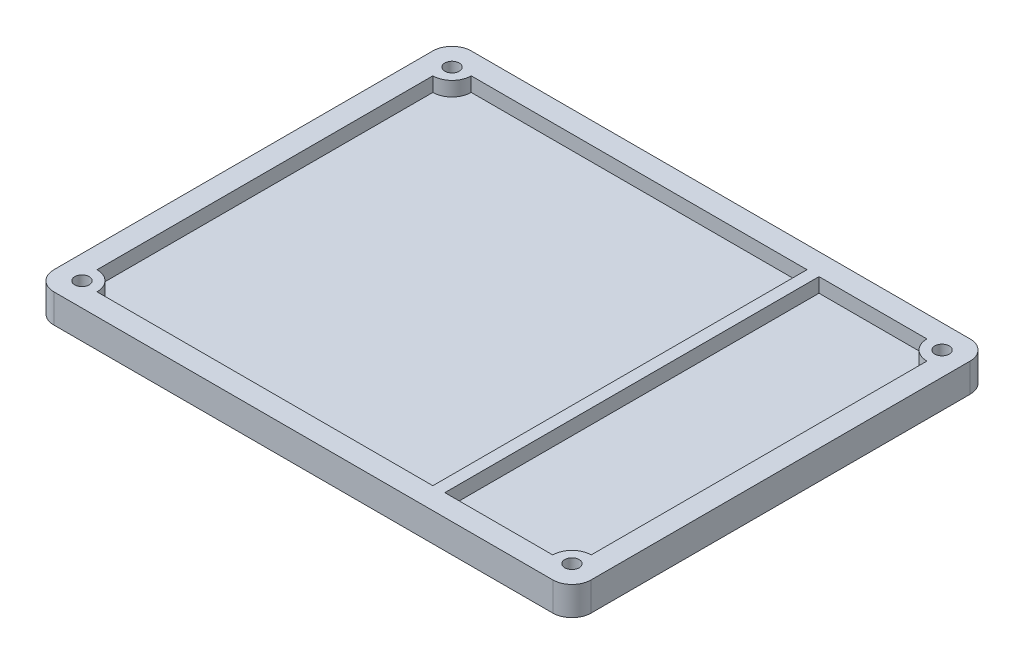
SolidWorks part; units mm, degrees
ref_plane "Front Plane" through (0, 0, 0) normal (0, 0, 1) x (1, 0, 0)
ref_plane "Top Plane" through (0, 0, 0) normal (0, 1, 0) x (1, 0, 0)
ref_plane "Right Plane" through (0, 0, 0) normal (1, 0, 0) x (0, 0, -1)
sketch "Sketch2" plane through (0, 0, 0) normal (0, 1, 0) x (1, 0, 0)
  line L0 (22.2847, 38.8731) -> (24.7847, 38.8731)
  line L1 (22.2847, -39.1269) -> (24.7847, -39.1269)
  line L2 (47.2847, 38.8731) -> (24.7847, 38.8731)
  line L3 (22.2847, 38.8731) -> (-47.7153, 38.8731)
  line L4 (51.2847, -35.1269) -> (51.2847, 34.8731)
  line L5 (24.7847, -39.1269) -> (47.2847, -39.1269)
  line L6 (-47.7153, -39.1269) -> (22.2847, -39.1269)
  line L7 (-51.7153, 34.8731) -> (-51.7153, -35.1269)
  line L8 (53.7847, -39.6269) -> (53.7847, 39.3731)
  line L9 (-52.2153, -41.6269) -> (51.7847, -41.6269)
  line L10 (-54.2153, -39.6269) -> (-54.2153, 39.3731)
  line L11 (51.7847, 41.3731) -> (-52.2153, 41.3731)
  circle A0 centre (50.8596, -38.7018) radius 1.5
  circle A1 centre (-51.2902, -38.7018) radius 1.5
  circle A2 centre (50.8596, 38.448) radius 1.5
  circle A3 centre (-51.2902, 38.448) radius 1.5
  arc A4 (47.2847, 38.8731) -> (51.2847, 34.8731) centre (51.2847, 38.8731) ccw
  arc A5 (51.2847, -35.1269) -> (47.2847, -39.1269) centre (51.2847, -39.1269) ccw
  arc A6 (-47.7153, -39.1269) -> (-51.7153, -35.1269) centre (-51.7153, -39.1269) ccw
  arc A7 (-51.7153, 34.8731) -> (-47.7153, 38.8731) centre (-51.7153, 38.8731) ccw
  arc A8 (53.7847, 39.3731) -> (51.7847, 41.3731) centre (51.7847, 39.3731) ccw
  arc A9 (51.7847, -41.6269) -> (53.7847, -39.6269) centre (51.7847, -39.6269) ccw
  arc A10 (-54.2153, -39.6269) -> (-52.2153, -41.6269) centre (-52.2153, -39.6269) ccw
  arc A11 (-52.2153, 41.3731) -> (-54.2153, 39.3731) centre (-52.2153, 39.3731) ccw
  point P4 (50.8596, 38.448)
extrude "Boss-Extrude1" add sketch "Sketch2" along normal blind 3
sketch "Sketch3" plane through (0, 0, 0) normal (0, -1, 0) x (1, 0, 0)
  line L0 (53.7847, 39.6269) -> (53.7847, -39.3731) construction
  line L1 (51.7847, -41.3731) -> (-52.2153, -41.3731) construction
  line L2 (-54.2153, -39.3731) -> (-54.2153, 39.6269) construction
  line L3 (-52.2153, 41.6269) -> (51.7847, 41.6269) construction
  line L4 (53.7847, 39.6269) -> (53.7847, -39.3731)
  line L5 (51.7847, -41.3731) -> (-52.2153, -41.3731)
  line L6 (-54.2153, -39.3731) -> (-54.2153, 39.6269)
  line L7 (-52.2153, 41.6269) -> (51.7847, 41.6269)
  arc A0 (53.7847, 39.6269) -> (51.7847, 41.6269) centre (51.7847, 39.6269) ccw construction
  arc A1 (51.7847, -41.3731) -> (53.7847, -39.3731) centre (51.7847, -39.3731) ccw construction
  arc A2 (-54.2153, -39.3731) -> (-52.2153, -41.3731) centre (-52.2153, -39.3731) ccw construction
  arc A3 (-52.2153, 41.6269) -> (-54.2153, 39.6269) centre (-52.2153, 39.6269) ccw construction
  arc A4 (53.7847, 39.6269) -> (51.7847, 41.6269) centre (51.7847, 39.6269) ccw
  arc A5 (51.7847, -41.3731) -> (53.7847, -39.3731) centre (51.7847, -39.3731) ccw
  arc A6 (-54.2153, -39.3731) -> (-52.2153, -41.3731) centre (-52.2153, -39.3731) ccw
  arc A7 (-52.2153, 41.6269) -> (-54.2153, 39.6269) centre (-52.2153, 39.6269) ccw
extrude "Boss-Extrude2" add sketch "Sketch3" along normal blind 3
sketch "Sketch4" plane through (0, 3, 0) normal (0, 1, 0) x (1, 0, 0)
  circle A0 centre (50.8596, 38.448) radius 1.5 construction
  circle A1 centre (50.8596, -38.7018) radius 1.5 construction
  circle A2 centre (-51.2902, -38.7018) radius 1.5 construction
  circle A3 centre (-51.2902, 38.448) radius 1.5 construction
  circle A4 centre (50.8596, 38.448) radius 1.5
  circle A5 centre (50.8596, -38.7018) radius 1.5
  circle A6 centre (-51.2902, -38.7018) radius 1.5
  circle A7 centre (-51.2902, 38.448) radius 1.5
extrude "Cut-Extrude1" cut sketch "Sketch4" against normal up to surface (6 mm away) up to face at (-0.2153, -3, 0.1269)
sketch "Sketch6" plane through (0, 3, 0) normal (0, 1, 0) x (1, 0, 0)
  line L6 (-56.2153, 39.3731) -> (-56.2153, -39.6269)
  line L7 (51.7847, 43.3731) -> (-52.2153, 43.3731)
  line L8 (-56.2153, 39.3731) -> (-56.2153, -39.6269)
  line L9 (51.7847, 43.3731) -> (-52.2153, 43.3731)
  line L15 (53.7847, -39.6269) -> (53.7847, 39.3731) construction
  line L16 (-52.2153, -41.6269) -> (51.7847, -41.6269) construction
  line L17 (55.7847, -39.6269) -> (55.7847, 39.3731)
  line L18 (-52.2153, -43.6269) -> (51.7847, -43.6269)
  line L19 (55.7847, -39.6269) -> (55.7847, 39.3731)
  line L20 (-52.2153, -43.6269) -> (51.7847, -43.6269)
  line L21 (-54.2153, 39.3731) -> (-54.2153, -39.6269) construction
  line L22 (51.7847, 41.3731) -> (-52.2153, 41.3731) construction
  line L23 (53.7847, -39.6269) -> (53.7847, 39.3731)
  line L24 (-52.2153, -41.6269) -> (51.7847, -41.6269)
  line L25 (-54.2153, 39.3731) -> (-54.2153, -39.6269)
  line L26 (51.7847, 41.3731) -> (-52.2153, 41.3731)
  arc A3 (-52.2153, 43.3731) -> (-56.2153, 39.3731) centre (-52.2153, 39.3731) ccw
  arc A4 (-52.2153, 43.3731) -> (-56.2153, 39.3731) centre (-52.2153, 39.3731) ccw
  arc A15 (53.7847, 39.3731) -> (51.7847, 41.3731) centre (51.7847, 39.3731) ccw construction
  arc A16 (51.7847, -41.6269) -> (53.7847, -39.6269) centre (51.7847, -39.6269) ccw construction
  arc A17 (-54.2153, -39.6269) -> (-52.2153, -41.6269) centre (-52.2153, -39.6269) ccw construction
  arc A18 (55.7847, 39.3731) -> (51.7847, 43.3731) centre (51.7847, 39.3731) ccw
  arc A19 (51.7847, -43.6269) -> (55.7847, -39.6269) centre (51.7847, -39.6269) ccw
  arc A20 (-56.2153, -39.6269) -> (-52.2153, -43.6269) centre (-52.2153, -39.6269) ccw
  arc A21 (55.7847, 39.3731) -> (51.7847, 43.3731) centre (51.7847, 39.3731) ccw
  arc A22 (51.7847, -43.6269) -> (55.7847, -39.6269) centre (51.7847, -39.6269) ccw
  arc A23 (-56.2153, -39.6269) -> (-52.2153, -43.6269) centre (-52.2153, -39.6269) ccw
  arc A24 (-52.2153, 41.3731) -> (-54.2153, 39.3731) centre (-52.2153, 39.3731) ccw construction
  arc A25 (53.7847, 39.3731) -> (51.7847, 41.3731) centre (51.7847, 39.3731) ccw
  arc A26 (51.7847, -41.6269) -> (53.7847, -39.6269) centre (51.7847, -39.6269) ccw
  arc A27 (-54.2153, -39.6269) -> (-52.2153, -41.6269) centre (-52.2153, -39.6269) ccw
  arc A28 (-52.2153, 41.3731) -> (-54.2153, 39.3731) centre (-52.2153, 39.3731) ccw
  dimension "D1" = 2
  dimension "D2" = 2
extrude "Boss-Extrude3" add sketch "Sketch6" against normal up to surface (6 mm away) up to face at (-51.2902, -3, -39.948)
sketch "Sketch7" plane through (0, -3, 0) normal (0, -1, 0) x (1, 0, 0)
  circle A0 centre (-51.2902, 38.7018) radius 3
  circle A1 centre (50.8596, 38.7018) radius 3
  circle A2 centre (-51.2902, -38.448) radius 3
  circle A3 centre (50.8596, -38.448) radius 3
  dimension "D1" = 6
  dimension "D2" = 6
  dimension "D3" = 6
  dimension "D4" = 6
extrude "Cut-Extrude2" cut sketch "Sketch7" against normal blind 2
sketch "Sketch10" plane through (0, 3, 0) normal (0, 1, 0) x (1, 0, 0)
  line L0 (24.7847, 38.8731) -> (24.7847, -39.1269)
  line L1 (47.2847, 38.8731) -> (-47.7153, 38.8731) construction
  line L2 (-47.7153, -39.1269) -> (47.2847, -39.1269) construction
  line L3 (22.2847, 38.8731) -> (22.2847, -39.1269)
  line L4 (51.2847, -35.1269) -> (51.2847, 34.8731) construction
  line L5 (22.2847, 38.8731) -> (24.7847, 38.8731)
  line L6 (22.2847, -39.1269) -> (24.7847, -39.1269)
  dimension "D1" = 26.5
  dimension "D2" = 2.5
extrude "Boss-Extrude4" add sketch "Sketch10" against normal up to surface (3 mm away) up to face at (-0.2153, 0, 0.1269)
sketch "Sketch11" plane through (0, -3, 0) normal (0, -1, 0) x (1, 0, 0)
  text T0 "VitaSync" font "Century Schoolbook" height 8
extrude "Cut-Extrude3" cut sketch "Sketch11" against normal blind 1.2
